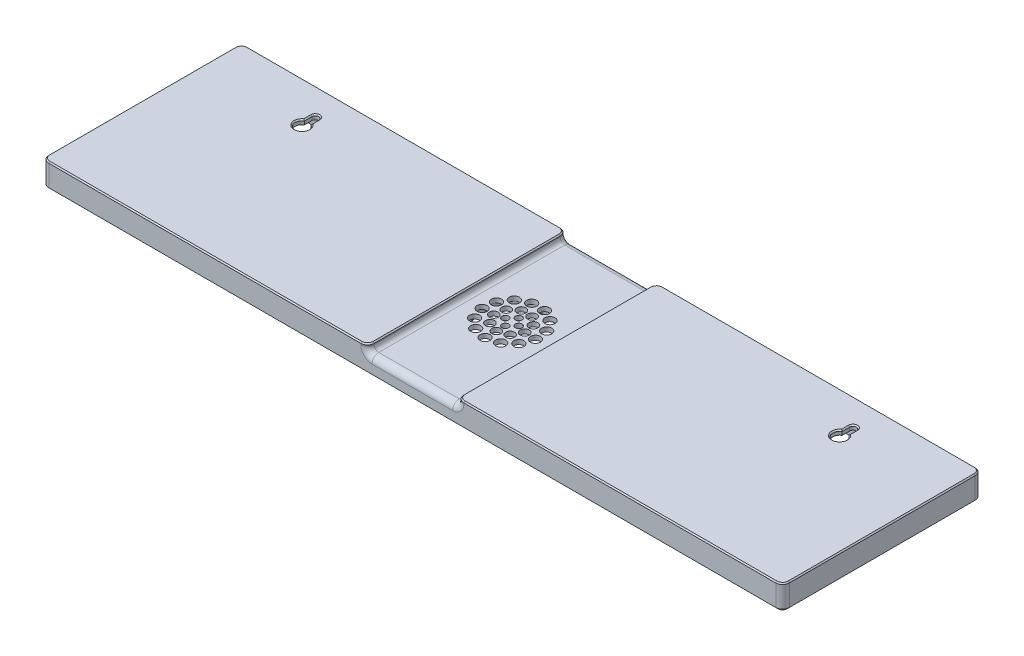
SolidWorks part; units mm, degrees
ref_plane "Front Plane" through (0, 0, 0) normal (0, 0, 1) x (1, 0, 0)
ref_plane "Top Plane" through (0, 0, 0) normal (0, 1, 0) x (1, 0, 0)
ref_plane "Right Plane" through (0, 0, 0) normal (1, 0, 0) x (0, 0, -1)
sketch "Sketch1" plane through (0, 0, 0) normal (0, 1, 0) x (1, 0, 0)
  line L1 (-163.25, 42.5) -> (163.25, 42.5)
  line L2 (-163.25, 42.5) -> (-163.25, -42.5)
  line L3 (-163.25, -42.5) -> (163.25, -42.5)
  line L4 (163.25, 42.5) -> (163.25, -42.5)
  line L5 (-163.25, 42.5) -> (163.25, -42.5) construction
  line L6 (-163.25, -42.5) -> (163.25, 42.5) construction
  line L7 (-161.25, 40.5) -> (161.25, 40.5)
  line L8 (-161.25, 40.5) -> (-161.25, -40.5)
  line L9 (-161.25, -40.5) -> (161.25, -40.5)
  line L10 (161.25, 40.5) -> (161.25, -40.5)
  line L11 (-161.25, 40.5) -> (161.25, -40.5) construction
  line L12 (-161.25, -40.5) -> (161.25, 40.5) construction
  point P0 (0, 0)
  point P6 (0, 0)
  dimension "D1" = 326.5
  dimension "D2" = 85
  dimension "D3" = 81
  dimension "D4" = 322.5
extrude "Boss-Extrude1" add sketch "Sketch1" along normal blind 10
sketch "Sketch2" plane through (0, 10, 0) normal (0, 1, 0) x (1, 0, 0)
  line L1 (-161.25, 40.5) -> (161.25, 40.5)
  line L2 (-161.25, 40.5) -> (-161.25, -40.5)
  line L3 (-161.25, -40.5) -> (161.25, -40.5)
  line L4 (161.25, 40.5) -> (161.25, -40.5)
  line L5 (-165.25, 44.5) -> (165.25, 44.5)
  line L6 (-165.25, 44.5) -> (-165.25, -44.5)
  line L7 (-165.25, -44.5) -> (165.25, -44.5)
  line L8 (165.25, 44.5) -> (165.25, -44.5)
  line L9 (-165.25, 44.5) -> (165.25, -44.5) construction
  line L10 (-165.25, -44.5) -> (165.25, 44.5) construction
  point P6 (0, 0)
  dimension "D1" = 4
  dimension "D2" = 4
extrude "Boss-Extrude2" add sketch "Sketch2" against normal blind 8
sketch "Sketch3" plane through (0, 10, 0) normal (0, 1, 0) x (1, 0, 0)
  line L1 (-165.25, 44.5) -> (165.25, 44.5)
  line L2 (-165.25, 44.5) -> (-165.25, -44.5)
  line L3 (-165.25, -44.5) -> (165.25, -44.5)
  line L4 (165.25, 44.5) -> (165.25, -44.5)
extrude "Boss-Extrude3" add sketch "Sketch3" along normal blind 2
fillet "Fillet1" radius 3 4 edges at (-161.25, 5, -40.5) (-161.25, 5, 40.5) (161.25, 5, 40.5) (161.25, 5, -40.5)
fillet "Fillet2" radius 2 4 edges at (-163.25, 1, -42.5) (-163.25, 1, 42.5) (163.25, 1, 42.5) (163.25, 1, -42.5)
fillet "Fillet3" radius 3 4 edges at (165.25, 7, -44.5) (165.25, 7, 44.5) (-165.25, 7, 44.5) (-165.25, 7, -44.5)
chamfer "Chamfer1" distance 0.5 angle 45 8 edges at (0, 12, 44.5) (164.3713, 12, 43.6213) (-164.3713, 12, 43.6213) (165.25, 12, 0) (-165.25, 12, 0) (164.3713, 12, -43.6213) (-164.3713, 12, -43.6213) (0, 12, -44.5)
sketch "Sketch4" plane through (0, 12, 0) normal (0, 1, 0) x (1, 0, 0)
  line L0 (0, 0) -> (0, 32.2227) construction
  line L1 (0, 32.2227) -> (120, 32.2227) construction
  line L2 (0, 32.2227) -> (-120, 32.2227) construction
  line L3 (-120, 32.2227) -> (-120, 26.2227) construction
  line L4 (120, 32.2227) -> (120, 26.2227) construction
  line L5 (-121.5, 32.2227) -> (-121.5, 28.8208)
  line L6 (-118.5, 32.2227) -> (-118.5, 28.8208)
  line L7 (118.5, 32.2227) -> (118.5, 28.8208)
  line L8 (121.5, 32.2227) -> (121.5, 28.8208)
  arc A0 (-121.5, 28.8208) -> (-118.5, 28.8208) centre (-120, 26.2227) ccw
  arc A1 (118.5, 28.8208) -> (121.5, 28.8208) centre (120, 26.2227) ccw
  arc A2 (-118.5, 32.2227) -> (-121.5, 32.2227) centre (-120, 32.2227) ccw
  arc A3 (121.5, 32.2227) -> (118.5, 32.2227) centre (120, 32.2227) ccw
  dimension "D3" = 6
  dimension "D4" = 6
  dimension "D7" = 3
  dimension "D8" = 3
  dimension "D1" = 120
  dimension "D2" = 120
  dimension "D5" = 6
  dimension "D6" = 6
extrude "Cut-Extrude1" cut sketch "Sketch4" against normal through all
chamfer "Chamfer2" distance 0.5 angle 45 8 edges at (118.5, 12, -30.5217) (120, 12, -33.7227) (121.5, 12, -30.5217) (120, 12, -23.2227) (-121.5, 12, -30.5217) (-120, 12, -33.7227) (-118.5, 12, -30.5217) (-120, 12, -23.2227)
sketch "Sketch7" plane through (0, 0, -44.5) normal (0, 0, -1) x (-1, 0, 0)
  line L0 (0, 0) -> (0, 9) construction
  line L1 (-161.25, 0) -> (161.25, 0) construction
  line L2 (0, 9) -> (-20, 9) construction
  line L3 (0, 9) -> (20, 9) construction
  line L4 (-162.25, 12) -> (162.25, 12) construction
  line L5 (-20, 9) -> (-20, 15.166)
  line L6 (-20, 15.166) -> (20, 15.166)
  line L7 (20, 15.166) -> (20, 9)
  line L8 (20, 9) -> (-20, 9)
  dimension "D1" = 20
  dimension "D2" = 20
  dimension "D3" = 3
extrude "Cut-Extrude3" cut sketch "Sketch7" against normal through all
sketch "Sketch8" plane through (0, 0, -44.5) normal (0, 0, -1) x (-1, 0, 0)
  line L0 (-20, 12) -> (-20, 9)
  line L1 (-20, 9) -> (20, 9)
  line L2 (20, 9) -> (20, 12)
  line L3 (20, 12) -> (22, 12)
  line L4 (20, 12) -> (162.25, 12) construction
  line L5 (22, 12) -> (22, 7)
  line L6 (22, 7) -> (-22, 7)
  line L7 (-22, 7) -> (-22, 12)
  line L8 (-162.25, 12) -> (-20, 12) construction
  line L13 (-20, 11.5) -> (-20, 12)
  line L14 (-20, 12) -> (-162.25, 12)
  line L15 (-162.25, 12) -> (-162.25, 11.5)
  line L16 (-162.25, 11.5) -> (-20, 11.5)
  line L18 (-20, 12) -> (-22, 12)
  dimension "D1" = 2
  dimension "D2" = 2
  dimension "D3" = 2
  dimension "D4" = 0
extrude "Boss-Extrude4" add sketch "Sketch8" against normal up to surface (89 mm away) up to face at (0, 8.5, 44.5)
fillet "Fillet4" radius 2 2 edges at (-20, 9, 0) (20, 9, 0)
chamfer "Chamfer3" distance 0.5 angle 45 4 edges at (-21, 12, 44.5) (21, 12, 44.5) (-21, 12, -44.5) (21, 12, -44.5)
fillet "Fillet5" radius 3 10 edges at (20, 11.25, 44.5) (19.4142, 9.5858, 44.5) (-20, 11.25, 44.5) (-19.4142, 9.5858, 44.5) (20, 11.25, -44.5) (19.4142, 9.5858, -44.5) (-20, 11.25, -44.5) (-19.4142, 9.5858, -44.5) (0, 9, 44.5) (0, 9, -44.5)
fillet "Fillet6" radius 2 2 edges at (-22, 10, 0) (22, 10, 0)
sketch "Sketch9" plane through (0, 7, 0) normal (0, -1, 0) x (1, 0, 0)
  circle A0 centre (0, 0) radius 14.25
  circle A1 centre (0, 0) radius 16.25
  dimension "D1" = 28.5
  dimension "D2" = 32.5
extrude "Boss-Extrude5" add sketch "Sketch9" along normal blind 3
sketch "Sketch10" plane through (0, 7, 0) normal (0, -1, 0) x (1, 0, 0)
  line L0 (0, 0) -> (0, 14.25) construction
  circle A0 centre (0, 0) radius 14.25 construction
  circle A1 centre (0, 3) radius 1.5
  circle A2 centre (0, 7) radius 2
  circle A3 centre (0, 12) radius 2.25
  circle A5 centre (4.4995, 5.3623) radius 2
  circle A8 centre (6.8937, 1.2155) radius 2
  circle A11 centre (6.0622, -3.5) radius 2
  circle A14 centre (2.3941, -6.5778) radius 2
  circle A17 centre (-2.3941, -6.5778) radius 2
  circle A20 centre (-6.0622, -3.5) radius 2
  circle A23 centre (-6.8937, 1.2155) radius 2
  circle A26 centre (-4.4995, 5.3623) radius 2
  circle A28 centre (-2.9544, 0.5209) radius 1.5 [skipped]
  circle A29 centre (-1.9284, 2.2981) radius 1.5 [skipped]
  circle A30 centre (-2.5981, -1.5) radius 1.5 [skipped]
  circle A31 centre (-1.0261, -2.8191) radius 1.5 [skipped]
  circle A32 centre (1.0261, -2.8191) radius 1.5 [skipped]
  circle A33 centre (2.9544, 0.5209) radius 1.5 [skipped]
  circle A34 centre (2.5981, -1.5) radius 1.5 [skipped]
  circle A35 centre (1.9284, 2.2981) radius 1.5 [skipped]
  circle A36 centre (3, 0) radius 1.5
  circle A37 centre (0, -3) radius 1.5
  circle A38 centre (-3, 0) radius 1.5
  circle A39 centre (-7.7135, 9.1925) radius 2.25 [skipped]
  circle A40 centre (-11.8177, 2.0838) radius 2.25 [skipped]
  circle A41 centre (-10.3923, -6) radius 2.25 [skipped]
  circle A42 centre (-4.1042, -11.2763) radius 2.25 [skipped]
  circle A43 centre (4.1042, -11.2763) radius 2.25 [skipped]
  circle A44 centre (10.3923, -6) radius 2.25 [skipped]
  circle A45 centre (11.8177, 2.0838) radius 2.25 [skipped]
  circle A46 centre (7.7135, 9.1925) radius 2.25 [skipped]
  circle A47 centre (5.5767, 10.6255) radius 2.25
  circle A48 centre (9.8758, 6.8168) radius 2.25
  circle A49 centre (11.9125, 1.4464) radius 2.25
  circle A50 centre (11.2202, -4.2553) radius 2.25
  circle A51 centre (7.9575, -8.9821) radius 2.25
  circle A52 centre (2.8718, -11.6513) radius 2.25
  circle A53 centre (-2.8718, -11.6513) radius 2.25
  circle A54 centre (-7.9575, -8.9821) radius 2.25
  circle A55 centre (-11.2202, -4.2553) radius 2.25
  circle A56 centre (-11.9125, 1.4464) radius 2.25
  circle A57 centre (-9.8758, 6.8168) radius 2.25
  circle A58 centre (-5.5767, 10.6255) radius 2.25
  dimension "D1" = 3
  dimension "D4" = 4
  dimension "D5" = 4.5
  dimension "D2" = 3
  dimension "D3" = 4
  dimension "D6" = 5
  dimension "D7" = 9
  dimension "D8" = 4
  dimension "D9" = 13
extrude "Cut-Extrude4" cut sketch "Sketch10" against normal through all
chamfer "Chamfer4" distance 0.5 angle 45 6 edges at (-20.3566, 12, -42.9186) (-20.3566, 12, 42.9186) (-20, 12, 0) (20.3566, 12, 42.9186) (20.3566, 12, -42.9186) (20, 12, 0)
sketch "Sketch12" plane through (0, 10, 0) normal (0, -1, 0) x (1, 0, 0)
  line L0 (-158.25, 40.5) -> (158.25, 40.5) construction
  line L1 (129.65, 20.5) -> (156.25, 20.5)
  line L2 (129.65, 20.5) -> (129.65, -14.5)
  line L3 (129.65, -14.5) -> (156.25, -14.5)
  line L4 (156.25, 20.5) -> (156.25, -14.5)
  line L5 (161.25, 37.5) -> (161.25, -37.5) construction
  line L7 (127.65, -16.5) -> (158.25, -16.5)
  line L8 (127.65, -16.5) -> (127.65, 22.5)
  line L9 (127.65, 22.5) -> (158.25, 22.5)
  line L10 (158.25, -16.5) -> (158.25, 22.5)
  line L11 (127.65, -16.5) -> (158.25, 22.5) construction
  line L12 (127.65, 22.5) -> (158.25, -16.5) construction
  point P8 (142.95, 3)
  dimension "D1" = 26.6
  dimension "D2" = 35
  dimension "D3" = 5
  dimension "20" = 20
  dimension "D4" = 2
  dimension "D5" = 2
  dimension "D6" = 2
  dimension "D7" = 2
extrude "Boss-Extrude6" add sketch "Sketch12" along normal blind 6
sketch "Sketch13" plane through (0, 10, 0) normal (0, -1, 0) x (1, 0, 0)
  line L0 (129.65, -14.5) -> (156.25, -14.5) construction
  line L1 (127.65, -12.5) -> (158.25, -12.5)
  line L2 (127.65, -12.5) -> (127.65, -16.5)
  line L3 (127.65, -16.5) -> (158.25, -16.5)
  line L4 (158.25, -12.5) -> (158.25, -16.5)
  line L5 (127.65, -12.5) -> (158.25, -16.5) construction
  line L6 (127.65, -16.5) -> (158.25, -12.5) construction
  point P0 (142.95, -14.5)
extrude "Boss-Extrude7" add sketch "Sketch13" along normal blind 2.7
sketch "Sketch14" plane through (0, 4, 0) normal (0, -1, 0) x (1, 0, 0)
  line L0 (156.25, -12.5) -> (156.25, 20.5) construction
  line L1 (156.25, 24.0241) -> (159.6238, 24.0241)
  line L2 (156.25, 24.0241) -> (156.25, 8.1247)
  line L3 (156.25, 8.1247) -> (159.6238, 8.1247)
  line L4 (159.6238, 24.0241) -> (159.6238, 8.1247)
  line L5 (135.6808, 24.5174) -> (150.9936, 24.5174)
  line L6 (135.6808, 24.5174) -> (135.6808, 18.4109)
  line L7 (135.6808, 18.4109) -> (150.9936, 18.4109)
  line L8 (150.9936, 24.5174) -> (150.9936, 18.4109)
  line L10 (125.8438, 11.915) -> (132.5475, 11.915)
  line L11 (125.8438, 11.915) -> (125.8438, -6.1679)
  line L12 (125.8438, -6.1679) -> (132.5475, -6.1679)
  line L13 (132.5475, 11.915) -> (132.5475, -6.1679)
  point P4 (125.8438, 11.915)
extrude "Cut-Extrude5" cut sketch "Sketch14" against normal up to surface (6 mm away) up to face at (142.95, 10, 4)
fillet "Fillet7" radius 2 5 edges at (150.9936, 7, 20.5) (135.6808, 7, 20.5) (129.65, 7, 11.915) (156.25, 7, 8.1247) (129.65, 7, -6.1679)
sketch "Sketch15" plane through (0, 0, -40.5) normal (0, 0, 1) x (1, 0, 0)
  line L0 (163.25, 2) -> (144.2097, 2) construction
  line L2 (142.7324, 8.8331) -> (145.6871, 8.8331)
  line L4 (142.7324, 4.4331) -> (145.6871, 4.4331)
  line L6 (139.6479, 8.8331) -> (148.7716, 4.4331) construction
  line L7 (139.6479, 4.4331) -> (148.7716, 8.8331) construction
  arc A0 (142.7324, 8.8331) -> (142.7324, 4.4331) centre (144.2097, 6.6331) ccw
  arc A1 (145.6871, 4.4331) -> (145.6871, 8.8331) centre (144.2097, 6.6331) ccw
  point P2 (144.2097, 6.6331)
  dimension "D1" = 5.3
  dimension "D2" = 4.4
extrude "Cut-Extrude6" cut sketch "Sketch15" against normal blind 12.7
sketch "Sketch19" plane through (0, 10, 0) normal (0, -1, 0) x (1, 0, 0)
  line L1 (37.7413, -4.0841) -> (58.7413, -4.0841)
  line L2 (37.7413, -4.0841) -> (37.7413, -25.3841)
  line L3 (37.7413, -25.3841) -> (58.7413, -25.3841)
  line L4 (58.7413, -4.0841) -> (58.7413, -25.3841)
  line L5 (37.7413, -4.0841) -> (58.7413, -25.3841) construction
  line L6 (37.7413, -25.3841) -> (58.7413, -4.0841) construction
  line L7 (35.7413, -2.0841) -> (60.7413, -2.0841)
  line L8 (35.7413, -2.0841) -> (35.7413, -27.3841)
  line L9 (35.7413, -27.3841) -> (60.7413, -27.3841)
  line L10 (60.7413, -2.0841) -> (60.7413, -27.3841)
  line L11 (35.7413, -2.0841) -> (60.7413, -27.3841) construction
  line L12 (35.7413, -27.3841) -> (60.7413, -2.0841) construction
  point P0 (48.2413, -14.7341)
  point P5 (48.2413, -14.7341)
  point P10 (49.8356, -2.1792)
  point P11 (48.2413, -14.7341)
  dimension "D1" = 21.3
  dimension "D2" = 21
  dimension "D3" = 2
  dimension "D4" = 2
extrude "Boss-Extrude8" add sketch "Sketch19" along normal blind 6
sketch "Sketch20" plane through (0, 4, 0) normal (0, -1, 0) x (1, 0, 0)
  line L0 (35.7413, -27.3841) -> (60.7413, -27.3841) construction
  line L1 (39.7413, -21.738) -> (56.7413, -21.738)
  line L2 (39.7413, -21.738) -> (39.7413, -33.0301)
  line L3 (39.7413, -33.0301) -> (56.7413, -33.0301)
  line L4 (56.7413, -21.738) -> (56.7413, -33.0301)
  line L5 (39.7413, -21.738) -> (56.7413, -33.0301) construction
  line L6 (39.7413, -33.0301) -> (56.7413, -21.738) construction
  line L7 (37.7413, -4.0841) -> (37.7413, -25.3841) construction
  point P0 (48.2413, -27.3841)
  dimension "D1" = 2
extrude "Cut-Extrude9" cut sketch "Sketch20" against normal up to surface (6 mm away) up to face at (-120, 10, -29.4972)
fillet "Fillet8" radius 2 2 edges at (39.7413, 7, -25.3841) (56.7413, 7, -25.3841)
fillet "Fillet9" radius 2 5 edges at (158.25, 7, -16.5) (127.65, 7, -16.5) (127.65, 7, 22.5) (35.7413, 7, -2.0841) (60.7413, 7, -2.0841)
fillet "Fillet10" radius 1 3 edges at (16.25, 4, 0) (14.25, 4, 0) (16.25, 7, 0)
